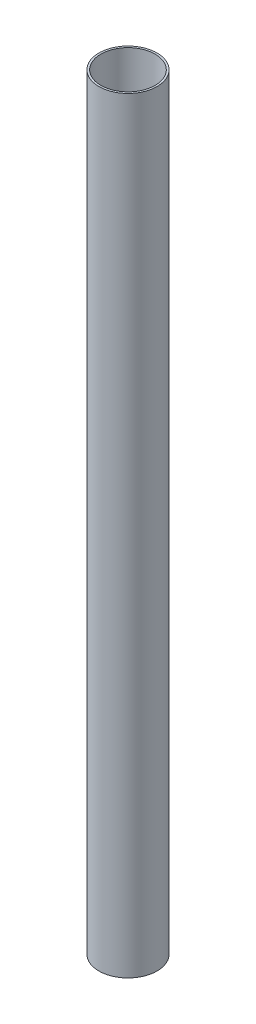
SolidWorks part; units mm, degrees
material "E-Glass Fiber"
ref_plane "Front Plane" through (0, 0, 0) normal (0, 0, 1) x (1, 0, 0)
ref_plane "Top Plane" through (0, 0, 0) normal (0, 1, 0) x (1, 0, 0)
ref_plane "Right Plane" through (0, 0, 0) normal (1, 0, 0) x (0, 0, -1)
sketch "Sketch1" plane through (0, 0, 0) normal (0, 0, 1) x (1, 0, 0)
  line L0 (0, 0) -> (0, -40.98) construction
  line L1 (28.9179, 30.8612) -> (28.9179, -731.1388) construction
  line L2 (26.9875, 30.8612) -> (28.9179, 30.8612)
  line L3 (26.9875, 30.8612) -> (26.9875, -731.1388)
  line L4 (26.9875, -731.1388) -> (28.9179, -731.1388)
  line L5 (28.9179, 30.8612) -> (28.9179, -731.1388)
revolve "Revolve1" add sketch "Sketch1" angle 360 about L0
